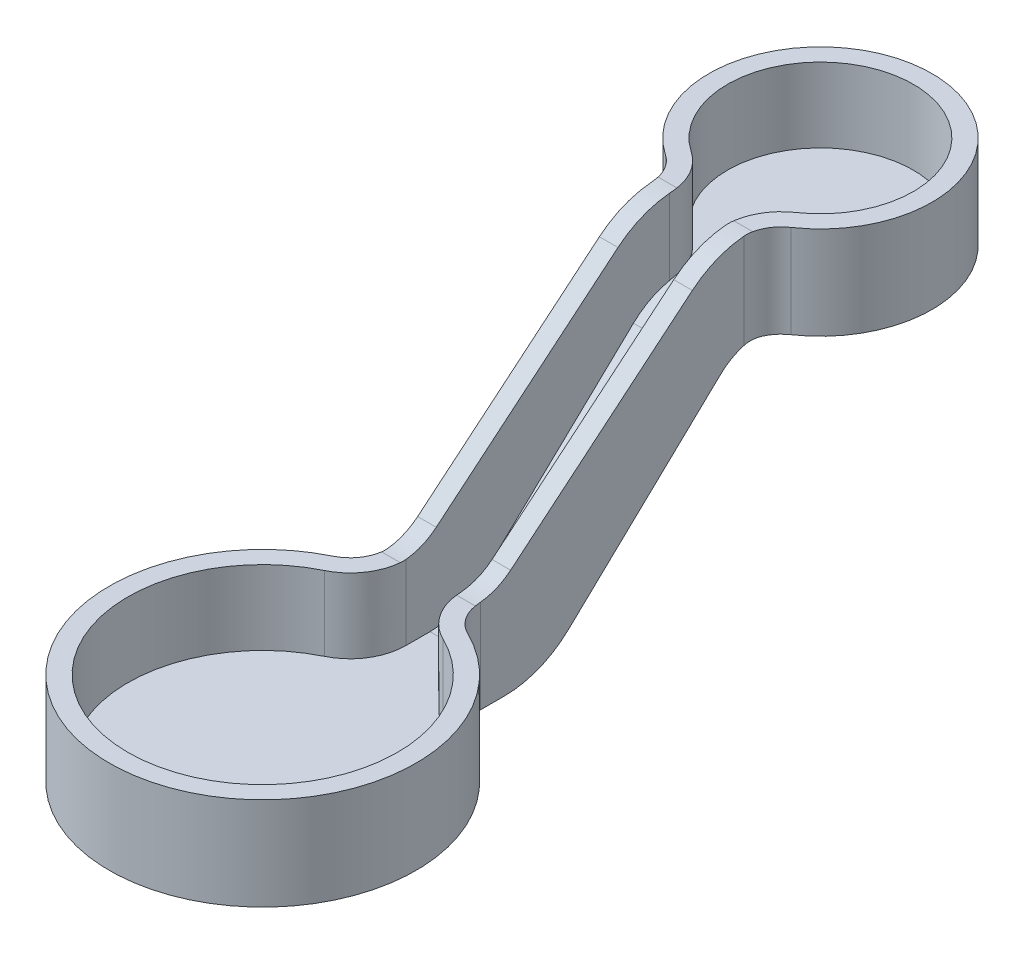
SolidWorks part; units mm, degrees
material "AISI 1020"
ref_plane "Front Plane" through (0, 0, 0) normal (0, 0, 1) x (1, 0, 0)
ref_plane "Top Plane" through (0, 0, 0) normal (0, 1, 0) x (1, 0, 0)
ref_plane "Right Plane" through (0, 0, 0) normal (1, 0, 0) x (0, 0, -1)
sketch "Sketch1" plane through (0, 0, 0) normal (0, 1, 0) x (1, 0, 0)
  circle A0 centre (0, 0) radius 82.5
  circle A1 centre (0, 0) radius 62.5 construction
  dimension "D1" = 20
  dimension "D2" = 125
extrude "Boss-Extrude1" add sketch "Sketch1" along normal blind 50
sketch "Sketch2" plane through (0, 0, 0) normal (0, 1, 0) x (1, 0, 0)
  line L0 (0, 0) -> (0, 300) construction
  circle A0 centre (0, 300) radius 60
  circle A1 centre (0, 300) radius 40 construction
  dimension "D1" = 20
  dimension "D2" = 80
  dimension "D3" = 300
extrude "Boss-Extrude2" add sketch "Sketch2" along normal blind 50 from offset 100 separate body
sketch "Sketch3" plane through (0, 0, 0) normal (1, 0, 0) x (0, 0, -1)
  line L0 (100, 0) -> (125, 0)
  line L1 (-82.5, 0) -> (82.5, 0) construction
  line L2 (125, 0) -> (230, 100)
  line L3 (300, 100) -> (230, 100)
  line L4 (0, 0) -> (0, 50)
  line L5 (82.5, 50) -> (-82.5, 50) construction
  line L6 (0, 50) -> (100, 50)
  line L7 (100, 50) -> (220, 150)
  line L8 (220, 150) -> (300, 150)
  line L9 (360, 150) -> (240, 150) construction
  line L10 (240, 100) -> (360, 100) construction
  line L11 (300, 100) -> (300, 150)
  line L13 (0, 0) -> (100, 0)
  line L14 (100, 50) -> (100, 0) construction
  dimension "D1" = 25
  dimension "D2" = 80
  dimension "D3" = 100
  dimension "D4" = 10
extrude "Boss-Extrude3" add sketch "Sketch3" along normal mid plane 50
fillet "Fillet1" radius 30 2 edges at (0, 50, -100) (0, 100, -230)
fillet "Fillet2" radius 50 2 edges at (0, 0, -125) (0, 150, -220)
fillet "Fillet3" radius 20 4 edges at (25, 25, -78.6209) (-25, 25, -78.6209) (-25, 125, -245.4564) (25, 125, -245.4564)
shell "Shell1" thickness 10 removed face at (0, 150, -272.0478) removed face at (-0.076, 146.7876, -225.7252) removed face at (0, 97.6822, -157.2187) removed face at (0.0366, 51.9598, -96.6957) removed face at (0, 50, -41.7965)
equation "\"A\"= 100"
equation "\"B\"= 100"
equation "\"C\"= 100"
equation "\"D\"= 100"
equation "\"E\"= 100"
